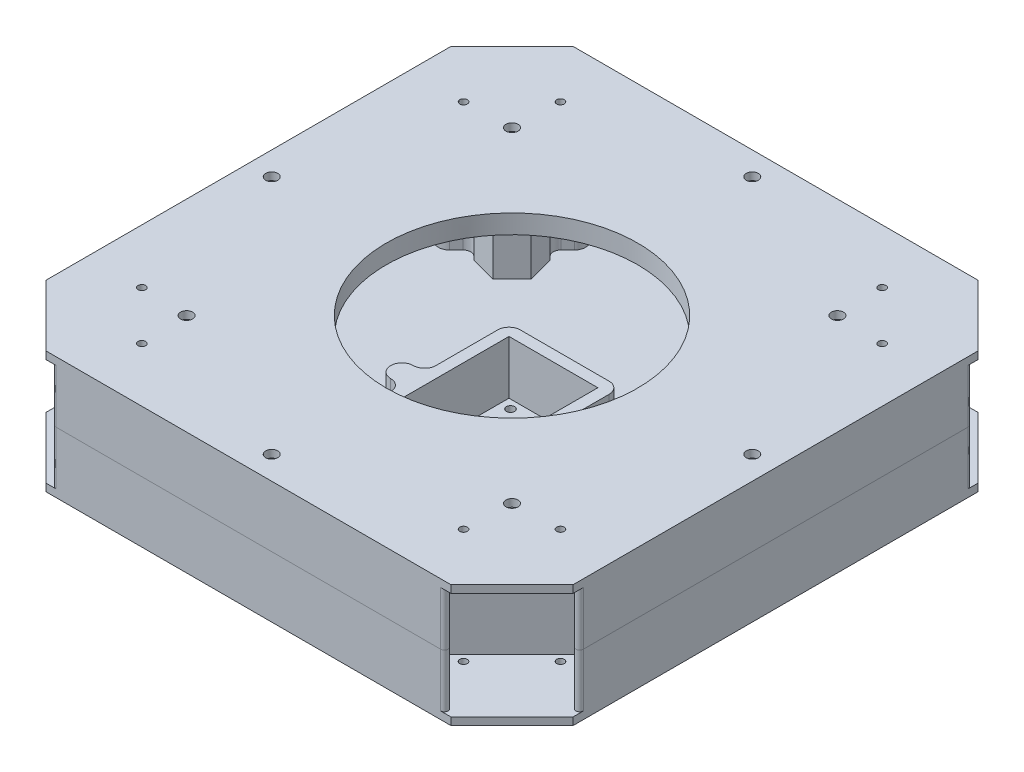
SolidWorks part; units mm, degrees
note: '?' marks a value the reader was unsure of.
other "Bottom"
other "Top" parameters "D1"=3, "D2"=3
ref_plane "Front Plane" through (0, 0, 0) normal (0, 0, 1) x (1, 0, 0)
ref_plane "Top Plane" through (0, 0, 0) normal (0, 1, 0) x (1, 0, 0)
ref_plane "Right Plane" through (0, 0, 0) normal (1, 0, 0) x (0, 0, -1)
ref_axis "Axis1" through (0, -1.62, 0) along (0, 1, 0)?
sketch "Sketch1" plane through (0, 0, 0) normal (0, 1, 0) x (1, 0, 0)
  line L0 (0, 0) -> (0, 70)
  line L1 (0, 70) -> (53.7365, 70)
  line L2 (53.7365, 70) -> (70, 53.7365)
  line L3 (70, 53.7365) -> (70, 0)
  line L4 (70, 0) -> (0, 0)
  line L5 (53.7365, 70) -> (39.5944, 55.8579) construction
  line L6 (39.5944, 55.8579) -> (55.8579, 39.5944) construction
  line L7 (55.8579, 39.5944) -> (70, 53.7365) construction
  line L8 (61.8683, 61.8683) -> (47.7261, 47.7261) construction
  line L9 (42.7057, 55.575) -> (49.1403, 49.1403) construction
  line L10 (49.1403, 49.1403) -> (55.575, 42.7057) construction
  line L11 (44.45, -978.9849) -> (44.45, 49021.0151) construction
  line L12 (61.8683, 61.8683) -> (71.4142, 71.4142) construction
  line L13 (71.4142, 71.4142) -> (78.9803, 78.9803) construction
  line L14 (77.566, 77.566) -> (71.1314, 84.0007) construction
  line L15 (77.566, 77.566) -> (84.0007, 71.1314) construction
  line L16 (82.2683, 100.1581) -> (100.1581, 82.2683) construction
  circle A0 centre (42.7057, 55.575) radius 1
  circle A1 centre (55.575, 42.7057) radius 1
  circle A2 centre (0, 0) radius 60 construction
  circle A3 centre (71.4142, 71.4142) radius 10 construction
  circle A4 centre (71.4142, 71.4142) radius 7 construction
  circle A5 centre (0, 0) radius 457.2 construction
  circle A6 centre (0, 0) radius 228.6 construction
  point P27 (91.2132, 91.2132)
  point P29 (0, 0)
  point P31 (0, 0)
  point P32 (0, 0)
  point P33 (0, 0)
  point P34 (0, 0)
  point P35 (0, 0)
  point P36 (0, 0)
  dimension "D4" = 2
  dimension "D7" = 120
  dimension "D11" = 20
  dimension "D12" = 14
  dimension "D16" = 914.4
  dimension "D17" = 457.2
  dimension "D1" = 44.45
  dimension "D2" = 23
  dimension "D3" = 20
  dimension "D5" = 18.2
  dimension "D6" = 2
  dimension "D8" = 70
  dimension "D9" = 44.2
  dimension "D10" = 10.7
  dimension "D13" = 40.2
  dimension "D14" = 25.3
  dimension "D15" = 28
extrude "Boss-Extrude1" add sketch "Sketch1" along normal blind 2
ref_plane "Plane1" through (0, 30.4, 0) normal (0, 1, 0) x (1, 0, 0)
ref_plane "Plane2" through (0, 16.2, 0) normal (0, 1, 0) x (1, 0, 0)
ref_plane "Plane3" through (0, 35.4, 0) normal (0, 1, 0) x (1, 0, 0)
sketch "Sketch4" plane through (0, 2, 0) normal (0, 1, 0) x (1, 0, 0)
  line L3 (49.2111, 70) -> (35.0689, 55.8579)
  line L4 (35.0689, 55.8579) -> (55.8579, 35.0689)
  line L5 (55.8579, 35.0689) -> (70, 49.2111)
  line L6 (55.8579, 39.3116) -> (70.1414, 53.5951)
  line L7 (39.3116, 55.8579) -> (55.8579, 39.3116)
  line L8 (53.5951, 70.1414) -> (39.3116, 55.8579)
  line L9 (55.8579, 39.3116) -> (70, 53.4537)
  line L10 (39.3116, 55.8579) -> (55.8579, 39.3116)
  line L11 (53.4537, 70) -> (39.3116, 55.8579)
  line L12 (51.3324, 72.1213) -> (35.0689, 55.8579) construction
  line L13 (49.2111, 70) -> (53.4537, 70)
  line L14 (55.8579, 35.0689) -> (72.1213, 51.3324) construction
  line L15 (70, 53.4537) -> (70, 49.2111)
  line L16 (70, 53.7365) -> (70, 0) construction
  line L17 (0, 70) -> (53.7365, 70) construction
  dimension "D1" = 0.2
  dimension "D2" = 3
extrude "Boss-Extrude2" add sketch "Sketch4" along normal up to surface (14.2 mm away) up to plane "Plane2"
fillet "Fillet1" radius 3 2 edges at (55.8579, 9.1, -35.0689) (35.0689, 9.1, -55.8579)
sketch "Sketch5" plane through (0, 2, 0) normal (0, 1, 0) x (1, 0, 0)
  line L0 (0, 70) -> (49.2111, 70)
  line L1 (49.2111, 70) -> (46.2111, 67)
  line L2 (46.2111, 67) -> (0, 67)
  line L3 (0, 67) -> (0, 70)
  line L4 (49.2111, 70) -> (35.0689, 55.8579) construction
  line L5 (0, 0) -> (35355.3391, 35355.3391) construction
  line L6 (67, 46.2111) -> (67, 0)
  line L7 (70, 49.2111) -> (67, 46.2111)
  line L8 (70, 0) -> (70, 49.2111)
  line L9 (67, 0) -> (70, 0)
  dimension "D1" = 3
extrude "Boss-Extrude3" add sketch "Sketch5" along normal up to surface (14.2 mm away) up to plane "Plane2"
fillet "Fillet2" radius 2 2 edges at (67, 9.1, -46.2111) (46.2111, 9.1, -67)
fillet "Fillet3" radius 1 2 edges at (70, 9.1, -53.4537) (53.4537, 9.1, -70)
sketch "Sketch6" plane through (0, 2, 0) normal (0, 1, 0) x (1, 0, 0)
  line L0 (61.8683, 61.8683) -> (47.7261, 47.7261) construction
  line L1 (45.6501, 40.7512) -> (46.5467, 44.0972) construction
  line L2 (46.5467, 44.0972) -> (44.0972, 46.5467) construction
  line L3 (44.0972, 46.5467) -> (40.7512, 45.6501) construction
  line L4 (40.7512, 45.6501) -> (39.8546, 42.3041) construction
  line L5 (39.8546, 42.3041) -> (42.3041, 39.8546) construction
  line L6 (42.3041, 39.8546) -> (45.6501, 40.7512) construction
  line L7 (39.5944, 55.8579) -> (55.8579, 39.5944) construction
  line L8 (45.8134, 40.5879) -> (46.7698, 44.157)
  line L9 (46.7698, 44.157) -> (44.157, 46.7698) construction
  line L10 (44.157, 46.7698) -> (40.5879, 45.8134)
  line L11 (40.5879, 45.8134) -> (39.6315, 42.2443)
  line L12 (39.6315, 42.2443) -> (42.2443, 39.6315)
  line L13 (42.2443, 39.6315) -> (45.8134, 40.5879)
  line L14 (35.0689, 55.8579) -> (55.8579, 35.0689) construction
  line L15 (38.1384, 48.2629) -> (36.2855, 41.3477)
  line L16 (36.2855, 41.3477) -> (41.3477, 36.2855)
  line L17 (41.3477, 36.2855) -> (48.2629, 38.1384)
  line L18 (40.5879, 45.8134) -> (38.1384, 48.2629) construction
  line L19 (37.6901, 46.5899) -> (36.2855, 41.3477) construction
  line L20 (41.3477, 36.2855) -> (46.5899, 37.6901) construction
  line L21 (38.1384, 48.2629) -> (40.4011, 50.5257)
  line L22 (40.4011, 50.5257) -> (44.157, 46.7698)
  line L23 (46.7698, 44.157) -> (50.5257, 40.4011)
  line L24 (50.5257, 40.4011) -> (48.2629, 38.1384)
  circle A0 centre (43.2007, 43.2007) radius 3 construction
  dimension "D2" = 6
  dimension "D3" = 3
  dimension "D1" = 0.2
extrude "Boss-Extrude4" add sketch "Sketch6" along normal up to surface (14.2 mm away) up to plane "Plane2"
sketch "Sketch7" plane through (0, 2, 0) normal (0, 1, 0) x (1, 0, 0)
  line L0 (0, 0) -> (0, 70) construction
  line L1 (3.695, 63.8) -> (1.8475, 67)
  line L2 (1.8475, 67) -> (-1.8475, 67) construction
  line L3 (-1.8475, 67) -> (-3.695, 63.8) construction
  line L4 (-3.695, 63.8) -> (-1.8475, 60.6) construction
  line L5 (-1.8475, 60.6) -> (1.8475, 60.6) construction
  line L6 (1.8475, 60.6) -> (3.695, 63.8)
  line L7 (46.2111, 67) -> (0, 67) construction
  line L8 (44.157, 46.7698) -> (40.5879, 45.8134) construction
  line L9 (1.8475, 60.6) -> (0, 60.6)
  line L10 (0, 60.6) -> (0, 57.6)
  line L11 (0, 67) -> (0, 0) construction
  line L12 (0, 57.6) -> (3.5796, 57.6)
  line L13 (3.5796, 57.6) -> (7.1591, 63.8)
  line L14 (7.1591, 63.8) -> (7.1591, 67)
  line L15 (7.1591, 67) -> (1.8475, 67)
  line L16 (2.7713, 62.2) -> (5.3694, 60.7) construction
  line L17 (41.3477, 36.2855) -> (48.2629, 38.1384) construction
  line L18 (-141421.3562, -141421.3562) -> (176776.6953, 176776.6953) construction
  line L19 (-141421.3562, -141421.3562) -> (176776.6953, 176776.6953) construction
  line L20 (60.6, 1.8475) -> (63.8, 3.695)
  line L21 (60.6, 1.8475) -> (60.6, 0)
  line L22 (60.6, 0) -> (57.6, 0)
  line L23 (57.6, 0) -> (57.6, 3.5796)
  line L24 (57.6, 3.5796) -> (63.8, 7.1591)
  line L25 (63.8, 7.1591) -> (67, 7.1591)
  line L26 (67, 7.1591) -> (67, 1.8475)
  line L27 (63.8, 3.695) -> (67, 1.8475)
  circle A0 centre (0, 63.8) radius 3.2 construction
  point P23 (0, 0)
extrude "Boss-Extrude5" add sketch "Sketch7" along normal up to surface (14.2 mm away) up to plane "Plane2"
sketch "Sketch8" plane through (0, 2, 0) normal (0, 1, 0) x (1, 0, 0)
  line L0 (67, 0) -> (60.6, 0) construction
  circle A0 centre (43.2007, 43.2007) radius 1.6
  circle A1 centre (0, 63.8) radius 1.6
  circle A2 centre (63.8, 0) radius 1.6
  circle A3 centre (43.2007, 43.2007) radius 3 construction
  circle A4 centre (0, 63.8) radius 3.2 construction
  point P14 (63.8, 0)
  dimension "D1" = 3.2
extrude "Cut-Extrude1" cut sketch "Sketch8" against normal through all
fillet "Fillet4" radius 2 4 edges at (50.5257, 9.1, -40.4011) (40.4011, 9.1, -50.5257) (67, 9.1, -7.1591) (7.1591, 9.1, -67)
pattern_circular "CirPattern1" count 4 over 360 about axis through (0, 0, 0) along (0, 1, 0) of bodies 106
combine bodies "Combine1" bodies to combine 106 107 108 109
mirror "Mirror1" about plane through (0, 16.2, 0) normal (0, 1, 0) of bodies 110 114
sketch "Sketch10" plane through (0, 2, 0) normal (0, 1, 0) x (1, 0, 0)
  line L1 (-11.5, -33.5) -> (11.5, -33.5) construction
  line L2 (-11.5, -33.5) -> (-11.5, 10.7) construction
  line L3 (-11.5, 10.7) -> (11.5, 10.7) construction
  line L4 (11.5, -33.5) -> (11.5, 10.7) construction
  line L5 (0, 10.7) -> (0, -33.5) construction
  line L6 (-11.5, -11.4) -> (11.5, -11.4) construction
  line L7 (39.5944, 55.8579) -> (55.8579, 39.5944) construction
  line L8 (47.7261, 47.7261) -> (78.9803, 78.9803) construction
  line L9 (61.8683, 61.8683) -> (47.7261, 47.7261) construction
  line L10 (78.9803, 78.9803) -> (86.5463, 71.4142) construction
  line L11 (86.5463, 71.4142) -> (78.9803, 63.8482) construction
  line L12 (78.9803, 63.8482) -> (71.4142, 71.4142) construction
  line L13 (6.5218, 10.7) -> (6.5218, 0) construction
  line L14 (6.5218, 0) -> (0, 0) construction
  line L15 (-11.8, -33.8) -> (11.8, -33.8)
  line L16 (11.8, -33.8) -> (11.8, 11)
  line L17 (-11.8, 11) -> (11.8, 11)
  line L18 (-11.8, -33.8) -> (-11.8, 11)
  line L19 (-14.8, -36.8) -> (14.8, -36.8)
  line L20 (14.8, -36.8) -> (14.8, 14)
  line L21 (-14.8, 14) -> (14.8, 14)
  line L22 (-14.8, -36.8) -> (-14.8, 14)
  line L24 (9.1, -31.5) -> (-9.1, -31.5) construction
  line L25 (9.1, -31.5) -> (9.1, 8.7) construction
  line L26 (9.1, 8.7) -> (-9.1, 8.7) construction
  line L27 (-9.1, -31.5) -> (-9.1, 8.7) construction
  line L28 (0, 8.7) -> (0, -31.5) construction
  line L29 (9.1, -11.4) -> (-9.1, -11.4) construction
  line L30 (42.7057, 55.575) -> (55.575, 42.7057) construction
  line L31 (55.575, 42.7057) -> (84.0007, 71.1314) construction
  circle A0 centre (0, 0) radius 10 construction
  circle A1 centre (71.4142, 71.4142) radius 10 construction
  point P5 (0, -11.4)
  point P29 (0, -11.4)
  point P33 (0, 0)
  point P36 (0, 0)
  point P37 (0, 0)
  point P38 (0, 0)
  point P39 (0, 0)
extrude "Boss-Extrude6" add sketch "Sketch10" along normal up to surface (14.2 mm away) up to plane "Plane2"
sketch "Sketch11" plane through (0, 2, 0) normal (0, 1, 0) x (1, 0, 0)
  circle A0 centre (-9.1, 8.7) radius 1.1
  circle A1 centre (9.1, 8.7) radius 1.1
  circle A2 centre (9.1, -31.5) radius 1.1
  circle A3 centre (-9.1, -31.5) radius 1.1
  circle A6 centre (0, 0) radius 10 construction
  circle A8 centre (0, 0) radius 5
  dimension "D1" = 2.2
  dimension "D2" = 10
extrude "Cut-Extrude2" cut sketch "Sketch11" against normal through all
sketch "Sketch13" plane through (0, 2, 0) normal (0, 1, 0) x (1, 0, 0)
  line L0 (-11.5, -11.4) -> (11.5, -11.4) construction
  line L1 (-20.8, -14.4) -> (-14.8, -14.4)
  line L2 (-20.8, -14.4) -> (-20.8, -8.4)
  line L3 (-20.8, -8.4) -> (-14.8, -8.4)
  line L4 (-14.8, -14.4) -> (-14.8, -8.4)
  line L5 (-17.8, -8.4) -> (-17.8, -14.4) construction
  line L6 (-20.8, -11.4) -> (-14.8, -11.4) construction
  line L7 (20.8, -14.4) -> (14.8, -14.4)
  line L8 (20.8, -14.4) -> (20.8, -8.4)
  line L9 (20.8, -8.4) -> (14.8, -8.4)
  line L10 (14.8, -14.4) -> (14.8, -8.4)
  line L11 (17.8, -8.4) -> (17.8, -14.4) construction
  line L12 (20.8, -11.4) -> (14.8, -11.4) construction
  line L13 (-14.8, -36.8) -> (-14.8, 14) construction
  line L14 (14.8, -36.8) -> (14.8, 14) construction
  point P0 (-17.8, -11.4)
  point P4 (17.8, -11.4)
  point P10 (0, 0)
  point P11 (0, 0)
  point P14 (0, 0)
  point P15 (0, 0)
  dimension "D1" = 6
extrude "Boss-Extrude7" add sketch "Sketch13" along normal up to surface (14.2 mm away) up to face at (0, 16.2, 11.4)
sketch "Sketch14" plane through (0, 2, 0) normal (0, 1, 0) x (1, 0, 0)
  line L0 (0, 10.7) -> (0, -33.5) construction
  line L1 (-1.5, -57.6) -> (1.5, -57.6)
  line L2 (-1.5, -57.6) -> (-1.5, -33.8)
  line L3 (-1.5, -33.8) -> (1.5, -33.8)
  line L4 (1.5, -57.6) -> (1.5, -33.8)
  line L5 (0, -33.8) -> (0, -57.6) construction
  line L6 (-1.5, -45.7) -> (1.5, -45.7) construction
  line L7 (-11.8, -33.8) -> (11.8, -33.8) construction
  line L8 (3.5796, -57.6) -> (-3.5796, -57.6) construction
  point P0 (0, -45.7)
  point P6 (0, 0)
  point P9 (0, 0)
  point P12 (0, 0)
  dimension "D1" = 3
extrude "Boss-Extrude8" add sketch "Sketch14" along normal up to surface (14.2 mm away) up to face at (0, 16.2, 11.4)
fillet "Fillet5" radius 3 14 edges at (-14.8, 9.1, 36.8) (14.8, 9.1, 36.8) (14.8, 9.1, -14) (-14.8, 9.1, -14) (14.8, 9.1, 14.4) (20.8, 9.1, 14.4) (20.8, 9.1, 8.4) (14.8, 9.1, 8.4) (-14.8, 9.1, 8.4) (-20.8, 9.1, 8.4) (-20.8, 9.1, 14.4) (-14.8, 9.1, 14.4) (1.5, 9.1, 36.8) (-1.5, 9.1, 36.8)
sketch "Sketch16" plane through (0, 2, 0) normal (0, 1, 0) x (1, 0, 0)
  line L0 (-11.5, -33.5) -> (11.5, -33.5) construction
  line L1 (9, -16.5) -> (-9, -16.5)
  line L2 (9, -16.5) -> (9, -6.5)
  line L3 (9, -6.5) -> (-9, -6.5)
  line L4 (-9, -16.5) -> (-9, -6.5)
  line L5 (0, -6.5) -> (0, -16.5) construction
  line L6 (9, -11.5) -> (-9, -11.5) construction
  point P0 (0, -11.5)
  point P6 (0, 0)
  point P9 (-9.3277, -4.8212)
  dimension "D1" = 17
  dimension "D2" = 18
  dimension "D3" = 10
extrude "Cut-Extrude3" cut sketch "Sketch16" against normal through all
sketch "Sketch18" plane through (0, 32.4, 0) normal (0, 1, 0) x (1, 0, 0)
  line L1 (14.8, 14) -> (16.9794, 16.0616) construction
  line L2 (0, 10.7) -> (0, -33.5) construction
  line L3 (17.8, -16.8867) -> (14.8, -16.8867) construction
  line L4 (14.8, -36.8) -> (14.8, 14) construction
  arc A0 (22.8, -16.8867) -> (-22.8, -16.8867) centre (0, 0) ccw construction
  arc A1 (26.818, -19.8626) -> (-26.818, -19.8626) centre (0, 0) ccw construction
  arc A2 (18.782, -13.9108) -> (-18.782, -13.9108) centre (0, 0) ccw construction
  arc A3 (18.782, -13.9108) -> (26.818, -19.8626) centre (22.8, -16.8867) ccw construction
  arc A4 (-26.818, -19.8626) -> (-18.782, -13.9108) centre (-22.8, -16.8867) ccw construction
  circle A5 centre (0, 0) radius 33.3725
  point P4 (0, 28.3725)
  dimension "D2" = 5
  dimension "D1" = 3
extrude "Cut-Extrude5" cut sketch "Sketch18" against normal through all
sketch "Sketch19" plane through (0, 30.4, 0) normal (0, -1, 0) x (1, 0, 0)
  circle A0 centre (0, 0) radius 33.3725 construction
  circle A1 centre (0, 0) radius 33.3725
  circle A2 centre (0, 0) radius 34.9725
  dimension "D1" = 1.6
extrude "Boss-Extrude10" add sketch "Sketch19" along normal blind 3
chamfer "Chamfer1" distance 3 angle 45 1 edges at (0, 30.4, 34.9725)
equation "\"D1@Fillet5\"=\"D2@Sketch10\""
equation "\"D1@Sketch13\"=2*\"D2@Sketch10\""
equation "\"D1@Sketch14\"=\"D2@Sketch10\""
equation "\"D1@Chamfer1\"=\"D1@Boss-Extrude10\""
